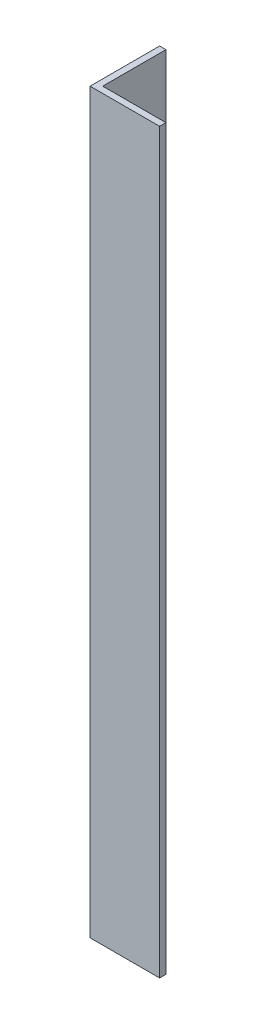
SolidWorks part; units mm, degrees
ref_plane "Спереди" through (0, 0, 0) normal (0, 0, 1) x (1, 0, 0)
ref_plane "Сверху" through (0, 0, 0) normal (0, 1, 0) x (1, 0, 0)
ref_plane "Справа" through (0, 0, 0) normal (1, 0, 0) x (0, 0, -1)
sketch "Эскиз1" plane through (0, 0, 0) normal (0, 1, 0) x (1, 0, 0)
  line L0 (0, 33) -> (0, 0)
  line L1 (0, 0) -> (33, 0)
extrude "Вытянуть-Тонкостенный1" add sketch "Эскиз1" along normal blind 350 thin thin type one direction reverse wall 3
